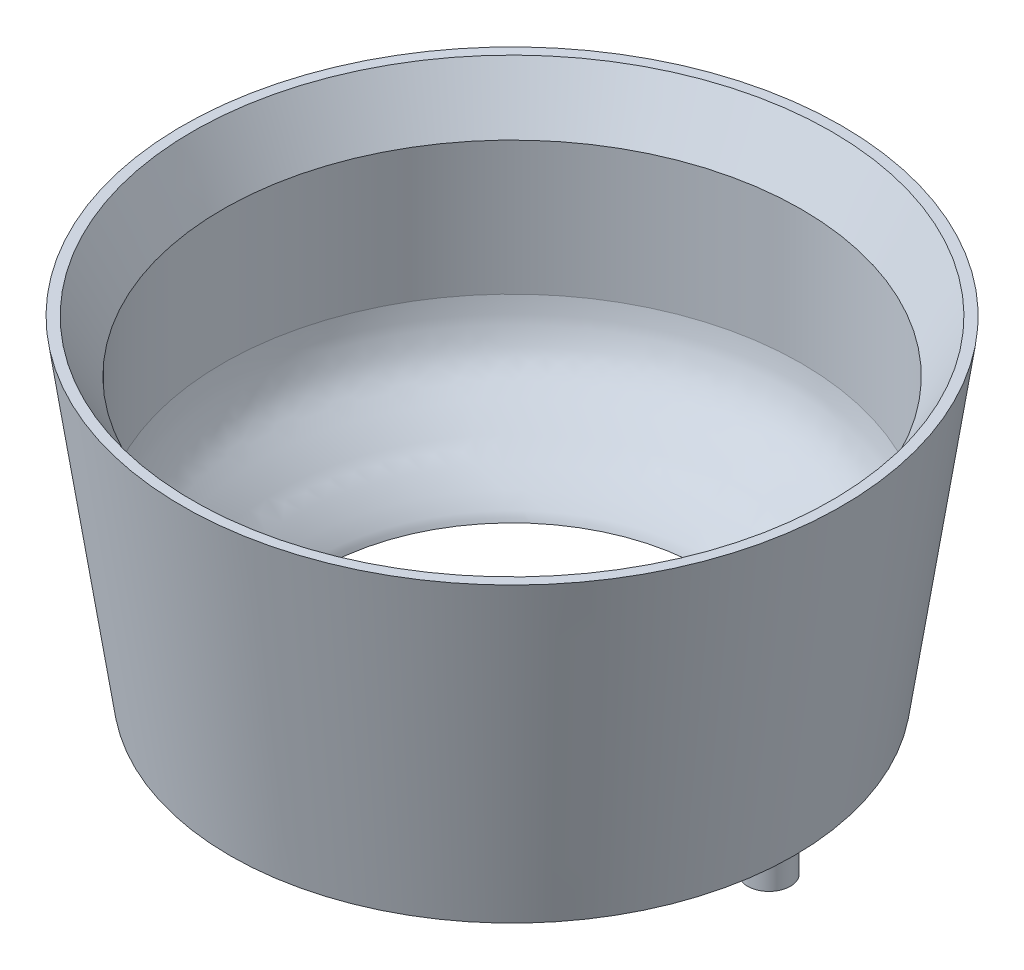
SolidWorks part; units mm, degrees
material "ABS PC"
ref_plane "Front Plane" through (0, 0, 0) normal (0, 0, 1) x (1, 0, 0)
ref_plane "Top Plane" through (0, 0, 0) normal (0, 1, 0) x (1, 0, 0)
ref_plane "Right Plane" through (0, 0, 0) normal (1, 0, 0) x (0, 0, -1)
sketch "Sketch1" plane through (0, 0, 0) normal (1, 0, 0) x (0, 0, -1)
  line L0 (26.0878, 274.978) -> (26.0878, 232.1195)
  line L2 (40.135, 299.274) -> (-40.135, 299.274) construction
  line L5 (0, 324) -> (3.2968, 324)
  line L8 (0, 324) -> (0, 0) construction
  line L9 (26.0878, 262.3641) -> (26.0878, 259.4973) construction
  line L12 (40.135, 302.9291) -> (40.135, 295.6188)
  line L16 (0, 0) -> (51.9362, 327.9125) construction
  line L17 (0, 324) -> (0, 332) construction
  line L18 (26.0878, 274.978) -> (26.0878, 268.978) construction
  line L19 (26.0878, 268.978) -> (26.0878, 248.978) construction
  line L20 (26.0878, 268.978) -> (42.6019, 268.978) construction
  line L21 (26.0878, 274.978) -> (43.5522, 274.978) construction
  line L22 (26.0878, 248.978) -> (39.4342, 248.978) construction
  line L23 (0, 0) -> (-51.9362, 327.9125) construction
  line L24 (-47.4003, 299.274) -> (-47.4003, 268.978) construction
  line L25 (-47.4003, 268.978) -> (-42.6019, 268.978) construction
  line L26 (0, 332) -> (0, 76.96) construction
  line L27 (0, 76.96) -> (400, 76.96) construction
  line L28 (0, 76.96) -> (-400, 76.96) construction
  line L29 (-200, 76.96) -> (-200, 183.96) construction
  line L30 (200, 76.96) -> (200, 183.96) construction
  line L31 (-200, 183.96) -> (-200, 182.57) construction
  line L32 (-200, 182.57) -> (400, 182.57) construction
  line L33 (-200, 182.57) -> (-400, 182.57) construction
  line L38 (0, 186.1152) -> (0, 324)
  line L39 (26.0878, 232.1195) -> (26.0878, 182.57) construction
  line L41 (21.6442, 226.0993) -> (26.0878, 226.0993)
  line L42 (26.0878, 226.0993) -> (26.0878, 186.1152)
  line L43 (26.0878, 186.1152) -> (0, 186.1152)
  line L44 (0, 0) -> (575.122, 0) construction
  arc A0 (-298.7691, 144.7791) -> (305.6579, 129.6043) centre (0, 0) cw construction
  spline S0 degree 3 poles (21.6442, 226.0993) (21.9584, 226.1509) (22.4049, 226.153) (22.896, 226.3321) (23.44, 226.7494) (24.2443, 227.2014) (25.0066, 227.9724) (25.5796, 228.9522) (25.8622, 230.393) (26.0228, 231.4436) (26.0878, 232.1195) knots 0 0 0 0 0.091924 0.112491 0.205673 0.333714 0.459267 0.602423 0.748839 1 1 1 1
  spline S1 degree 3 poles (3.2968, 324) (4.1972, 323.8396) (5.699, 323.816) (7.6935, 323.4297) (9.2722, 323.1563) (10.7507, 322.8538) (12.1816, 322.5577) (13.6372, 322.313) (14.8643, 321.9117) (15.9115, 321.5662) (16.81, 321.2491) (17.7339, 321.0149) (18.8379, 320.6416) (19.931, 320.1935) (21.0686, 319.6948) (22.141, 319.2627) (23.2156, 318.6856) (24.4371, 318.1163) (25.6762, 317.3518) (27.1066, 316.7518) (28.4318, 315.7832) (29.7322, 314.8939) (31.058, 313.93) (32.1959, 312.8581) (33.3378, 311.8503) (34.4539, 310.9646) (35.3895, 309.8867) (36.5078, 309.0949) (37.2942, 308.0208) (38.1233, 307.1238) (38.9048, 306.0961) (39.4724, 304.6349) (40.2774, 303.734) (40.135, 302.9291) knots 0 0 0 0 0.061585 0.100795 0.136831 0.1697 0.202569 0.235438 0.269088 0.289473 0.309858 0.333319 0.353706 0.388423 0.412965 0.437514 0.46634 0.495168 0.528354 0.564387 0.59925 0.638593 0.670824 0.709635 0.743897 0.773612 0.805519 0.839783 0.864953 0.89467 0.922395 0.951224 1 1 1 1
  spline S2 degree 3 poles (40.135, 295.6188) (39.9636, 294.7131) (39.7869, 293.3689) (39.1095, 291.6901) (38.6019, 290.4599) (37.8418, 289.2392) (36.9195, 288.2279) (35.9232, 287.2651) (34.974, 286.2515) (33.8311, 285.3463) (32.8233, 284.2966) (31.8701, 283.2868) (30.7668, 282.4387) (29.8742, 281.4644) (28.8604, 280.5152) (28.0567, 279.5119) (27.1438, 278.5569) (26.4968, 277.0287) (26.0081, 275.8567) (26.0878, 274.978) knots 0 0 0 0 0.108356 0.15601 0.210945 0.263562 0.322855 0.370186 0.4254 0.484692 0.539909 0.595126 0.646549 0.701764 0.749093 0.808384 0.85195 0.901837 1 1 1 1
  point P10 (0, 299.274)
  point P63 (0, 299.274)
  dimension "D3" = 9
  dimension "D1" = 40.135
  dimension "D2" = 324
  dimension "D4" = 8
  dimension "D5" = 3.2968
  dimension "D6" = 4.4435
  dimension "D7" = 6.0202
  dimension "D8" = 7.7403
  dimension "D9" = 6
  dimension "D10" = 20
  dimension "D11" = 9.317
  dimension "D12" = 10.7504
  dimension "D13" = 255.04
  dimension "D14" = 107
  dimension "D15" = 107
  dimension "D16" = 332
  dimension "D17" = 105.61
  dimension "D18" = 105.61
  dimension "D19" = 12.1838
  dimension "D20" = 13.6172
  dimension "D21" = 15.0506
  dimension "D22" = 15.9106
  dimension "D23" = 16.7707
  dimension "D24" = 17.7739
  dimension "D25" = 18.6341
  dimension "D26" = 20.0676
  dimension "D27" = 21.0708
  dimension "D28" = 22.0743
  dimension "D29" = 23.2209
  dimension "D30" = 24.3677
  dimension "D31" = 25.6578
  dimension "D32" = 27.0911
  dimension "D33" = 28.3811
  dimension "D34" = 29.8146
  dimension "D35" = 30.9613
  dimension "D36" = 32.2513
  dimension "D37" = 33.3981
  dimension "D38" = 34.4014
  dimension "D39" = 35.4048
  dimension "D40" = 36.5516
  dimension "D41" = 37.2681
  dimension "D42" = 38.1282
  dimension "D43" = 38.8449
  dimension "D44" = 39.4183
  dimension "D45" = 39.9917
  dimension "D46" = 323.8567
  dimension "D47" = 323.7133
  dimension "D48" = 323.4267
  dimension "D49" = 323.1399
  dimension "D50" = 322.8533
  dimension "D51" = 322.5666
  dimension "D52" = 322.2799
  dimension "D53" = 321.8499
  dimension "D54" = 321.5632
  dimension "D55" = 321.2765
  dimension "D56" = 320.9899
  dimension "D57" = 320.7031
  dimension "D58" = 320.1297
  dimension "D59" = 319.6998
  dimension "D60" = 319.2698
  dimension "D61" = 318.6965
  dimension "D62" = 318.1231
  dimension "D63" = 317.4064
  dimension "D64" = 316.6897
  dimension "D65" = 315.8296
  dimension "D66" = 314.8263
  dimension "D67" = 313.9663
  dimension "D68" = 312.8195
  dimension "D69" = 311.8162
  dimension "D70" = 310.9562
  dimension "D71" = 309.9528
  dimension "D72" = 308.9493
  dimension "D73" = 308.0893
  dimension "D74" = 307.086
  dimension "D75" = 306.0826
  dimension "D76" = 304.9359
  dimension "D77" = 303.9325
  dimension "D78" = 302.9291
sketch "Sketch2" plane through (0, 0, 0) normal (1, 0, 0) x (0, 0, -1)
  line L0 (0, 324) -> (3.2968, 324) construction
  line L1 (26.5078, 274.997) -> (26.5078, 273.8486)
  line L2 (40.5477, 295.5407) -> (40.5477, 314.2386)
  line L3 (40.135, 295.6188) -> (40.135, 302.9302) construction
  line L4 (40.135, 295.6188) -> (26.0878, 274.978) construction
  line L5 (0, 324.42) -> (3.4084, 324.42) construction
  line L6 (3.2968, 324) -> (40.135, 302.9302) construction
  line L7 (3.4084, 324.42) -> (40.555, 303.1738) construction
  line L8 (26.0878, 274.978) -> (26.0878, 232.1195) construction
  line L9 (40.555, 295.4895) -> (26.435, 274.7417) construction
  line L10 (0, 5) -> (0, 407.9498) construction
  line L12 (26.5078, 273.8486) -> (38.5078, 273.8486) construction
  line L13 (26.5078, 274.997) -> (26.5078, 232.1195) construction
  line L14 (38.5078, 273.8486) -> (45.76, 323.5611) construction
  line L17 (40.5477, 314.2386) -> (45.93, 323.5611) construction
  line L18 (45.93, 323.5611) -> (45.76, 323.5611) construction
  line L19 (0, 186.1152) -> (0, 324) construction
  line L20 (0, 324) -> (0, 332) construction
  line L21 (40.555, 295.4895) -> (40.555, 303.1738) construction
  line L22 (0, 5) -> (47.1644, 328.2999) construction
  line L23 (45.93, 323.5611) -> (46.473, 323.5611) construction
  line L24 (46.473, 323.5611) -> (39.2208, 273.8486) construction
  line L25 (39.2208, 273.8486) -> (26.5078, 273.8486)
  line L26 (44.7753, 321.5611) -> (46.1813, 321.5611)
  line L27 (44.7753, 321.5611) -> (40.5477, 314.2386)
  line L28 (46.1813, 321.5611) -> (39.2208, 273.8486)
  spline S0 degree 1 poles (40.5477, 295.5407) (26.5078, 274.997) knots 0 0 1 1 construction
  spline S1 degree 3 poles (40.135, 295.6188) (39.9636, 294.7131) (39.7869, 293.3689) (39.1095, 291.6901) (38.6019, 290.4599) (37.8418, 289.2392) (36.9195, 288.2279) (35.9232, 287.2651) (34.974, 286.2515) (33.8311, 285.3463) (32.8233, 284.2966) (31.8701, 283.2868) (30.7668, 282.4387) (29.8742, 281.4644) (28.8604, 280.5152) (28.0567, 279.5119) (27.1438, 278.5569) (26.4968, 277.0287) (26.0081, 275.8567) (26.0878, 274.978) knots 0 0 0 0 0.108356 0.15601 0.210945 0.263562 0.322855 0.370186 0.4254 0.484692 0.539909 0.595126 0.646549 0.701764 0.749093 0.808384 0.85195 0.901837 1 1 1 1 construction
  spline S2 degree 3 poles (40.5477, 295.5407) (40.4477, 295.0127) (40.2928, 293.9708) (39.9309, 292.5875) (39.5162, 291.5815) (39.1084, 290.578) (38.4397, 289.317) (37.3314, 288.0326) (36.3684, 287.1154) (35.6302, 286.3401) (35.0165, 285.7627) (34.3943, 285.2472) (33.6355, 284.5566) (32.9204, 283.7714) (32.1297, 282.9861) (31.4852, 282.4595) (30.915, 281.9635) (30.3717, 281.3913) (29.7828, 280.8046) (29.2276, 280.2622) (28.7248, 279.6749) (28.1804, 279.0397) (27.6518, 278.4702) (27.3081, 277.8768) (26.9952, 277.1272) (26.598, 276.1645) (26.4648, 275.4705) (26.5078, 274.997) knots 0 0 0 0 0.062544 0.125088 0.15636 0.187632 0.250176 0.31272 0.375264 0.406536 0.437808 0.46908 0.500352 0.562896 0.594168 0.62544 0.656713 0.687985 0.719257 0.750529 0.781801 0.813073 0.844345 0.875617 0.906889 0.938161 1.000705 1.000705 1.000705 1.000705
  point P38 (0, 328)
  dimension "D4" = 1.1484
  dimension "D5" = 8.3
  dimension "D6" = 30
  dimension "D7" = 45.93
  dimension "D8" = 40.39
  dimension "D9" = 8.3
  dimension "D10" = 40.5477
  dimension "D3" = 12
  dimension "D11" = 18.6979
  dimension "D12" = 2
  dimension "D13" = 5
  dimension "D1" = 0.42
  dimension "D2" = 0.42
revolve "Revolve6" add sketch "Sketch2" angle 360 about L10
sketch "Sketch3" plane through (0, 0, 0) normal (1, 0, 0) x (0, 0, -1)
  line L0 (44.1979, 321.5611) -> (40.5477, 314.2386) construction
  line L3 (46.1813, 321.5611) -> (-46.1813, 321.5611) construction
  line L4 (44.7753, 321.5611) -> (-44.7753, 321.5611) construction
  line L5 (40.5477, 314.2386) -> (-40.5477, 314.2386) construction
  line L6 (40.5477, 314.2386) -> (54.812, 333.8718)
  line L8 (54.812, 333.8718) -> (54.812, 347.837)
  line L9 (54.812, 347.837) -> (0, 347.837)
  line L10 (0, 347.837) -> (0, 311.6751)
  line L11 (0, 186.1152) -> (0, 324) construction
  line L12 (0, 311.6751) -> (40.5477, 311.6751)
  line L13 (40.5477, 311.6751) -> (40.5477, 314.2386)
  dimension "D1" = 36
  dimension "D2" = 54.812
revolve "Cut-Revolve1" [suppressed] cut sketch "Sketch3" angle 360 about L10
sketch "Sketch4" plane through (0, 273.8486, 0) normal (0, -1, 0) x (1, 0, 0)
  line L0 (0, 0) -> (36, 0) construction
  line L1 (0, 0) -> (-31.1769, 18) construction
  circle A0 centre (0, 0) radius 36 construction
  circle A1 centre (-31.1769, 18) radius 3
  circle A2 centre (36, 0) radius 3
  dimension "D1" = 72
  dimension "D3" = 6
  dimension "D4" = 6
  dimension "D2" = 150
extrude "Boss-Extrude1" add sketch "Sketch4" along normal blind 2
sketch "Sketch5" [suppressed] plane through (0, 263.8486, 0) normal (0, -1, 0) x (1, 0, 0)
  circle A0 centre (36, 0) radius 3.175
  circle A1 centre (-31.1769, 18) radius 3.175
  dimension "D1" = 6.35
  dimension "D2" = 6.35
extrude "Boss-Extrude2" [suppressed] add sketch "Sketch5" along normal blind 5
chamfer "Chamfer2" [suppressed] distance 9 angle 4
sketch "Sketch7" plane through (0, 0, 0) normal (1, 0, 0) x (0, 0, -1)
  line L0 (0, 5) -> (0, 407.9498) construction
  line L1 (26.5078, 273.8486) -> (39.2208, 273.8486) construction
  line L2 (39.2208, 273.8486) -> (39.2208, 272.3194)
  line L4 (26.5078, 273.8486) -> (26.5078, 274.3486)
  line L5 (26.5078, 274.3486) -> (39.2208, 274.3486)
  line L6 (39.2208, 274.3486) -> (39.2208, 273.8486)
  circle A0 centre (0, -0.122) radius 275.25 construction
  arc A1 (39.2208, 272.3194) -> (26.5078, 273.8486) centre (0, -0.122) ccw
  dimension "D1" = 550.5
  dimension "D2" = 0.5
revolve "Revolve7" add sketch "Sketch7" angle 360 about L10
sketch "Sketch12" plane through (0, 0, 0) normal (1, 0, 0) x (0, 0, -1)
  line L0 (26.5078, 273.8486) -> (26.5078, 277.3648) construction
  line L1 (26.0878, 277.4046) -> (26.0878, 267.4046)
  line L2 (26.0878, 274.978) -> (26.0878, 232.1195) construction
  line L3 (26.0878, 267.4046) -> (40.0878, 267.4046)
  line L4 (40.0878, 267.4046) -> (40.0878, 275.7304)
  line L5 (0, -0.122) -> (0, 301.1246) construction
  line L6 (0, 5) -> (0, 407.9498) construction
  circle A0 centre (0, -0.122) radius 278.75 construction
  arc A1 (40.0878, 275.7304) -> (26.0878, 277.4046) centre (0, -0.122) ccw
  dimension "D1" = 557.5
  dimension "D2" = 10
  dimension "D3" = 14
revolve "Cut-Revolve3" cut sketch "Sketch12" angle 360 about L10
extrude "Boss-Extrude3" add sketch "Sketch4<2>" along normal blind 2 and the other way up to next
sketch "Sketch4<2>" plane through (0, 273.8486, 0) normal (0, -1, 0) x (1, 0, 0) same geometry as "Sketch4"
sketch "Sketch13" plane through (0, 271.8486, 0) normal (0, -1, 0) x (1, 0, 0)
  circle A0 centre (-31.1769, 18) radius 1.5
  circle A1 centre (36, 0) radius 1.5
  dimension "D1" = 3
  dimension "D2" = 3
extrude "Cut-Extrude1" cut sketch "Sketch13" against normal blind 6
sketch "Sketch14" plane through (0, 271.8486, 0) normal (0, -1, 0) x (1, 0, 0)
  circle A0 centre (-31.1769, 18) radius 2
  circle A1 centre (36, 0) radius 2
  dimension "D1" = 4
  dimension "D2" = 4
extrude "Cut-Extrude2" cut sketch "Sketch14" against normal blind 0.5
chamfer "Chamfer3" distance 0.55 angle 45 2 edges at (36, 271.8486, -2) (-31.1769, 271.8486, 16)
